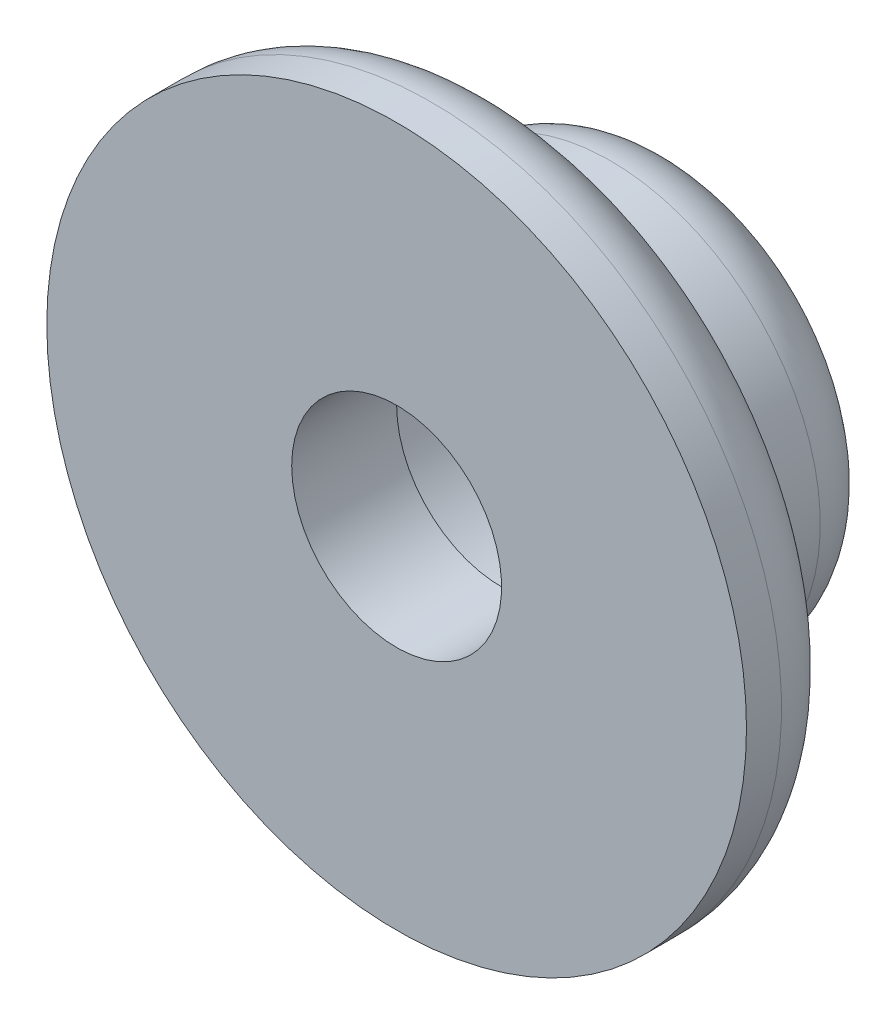
SolidWorks part; units mm, degrees
ref_plane "前视基准面" through (0, 0, 0) normal (0, 0, 1) x (1, 0, 0)
ref_plane "上视基准面" through (0, 0, 0) normal (0, 1, 0) x (1, 0, 0)
ref_plane "右视基准面" through (0, 0, 0) normal (1, 0, 0) x (0, 0, -1)
sketch "草图1" plane through (0, 0, 0) normal (0, 0, 1) x (1, 0, 0)
  circle A0 centre (0, 0) radius 10
  dimension "D1" = 20
extrude "凸台-拉伸1" add sketch "草图1" along normal blind 8
sketch "草图2" plane through (0, 0, 0) normal (0, 0, -1) x (-1, 0, 0)
  circle A0 centre (0, 0) radius 4.15
  dimension "D1" = 8.3
extrude "切除-拉伸1" cut sketch "草图2" against normal blind 5
sketch "草图3" plane through (0, 0, 0) normal (0, 0, -1) x (-1, 0, 0)
  circle A0 centre (0, 0) radius 6
  circle A1 centre (0, 0) radius 11.1887
  dimension "D1" = 12
extrude "切除-拉伸2" cut sketch "草图3" against normal blind 5
fillet "圆角1" radius 0.5 1 edges at (-4.15, 0, 0)
fillet "圆角2" radius 2 2 edges at (-10, 0, 5) (-6, 0, 0)
sketch "草图4" plane through (0, 0, 5) normal (0, 0, -1) x (-1, 0, 0)
  circle A0 centre (0, 0) radius 3
  dimension "D1" = 6
extrude "切除-拉伸3" cut sketch "草图4" against normal through all
